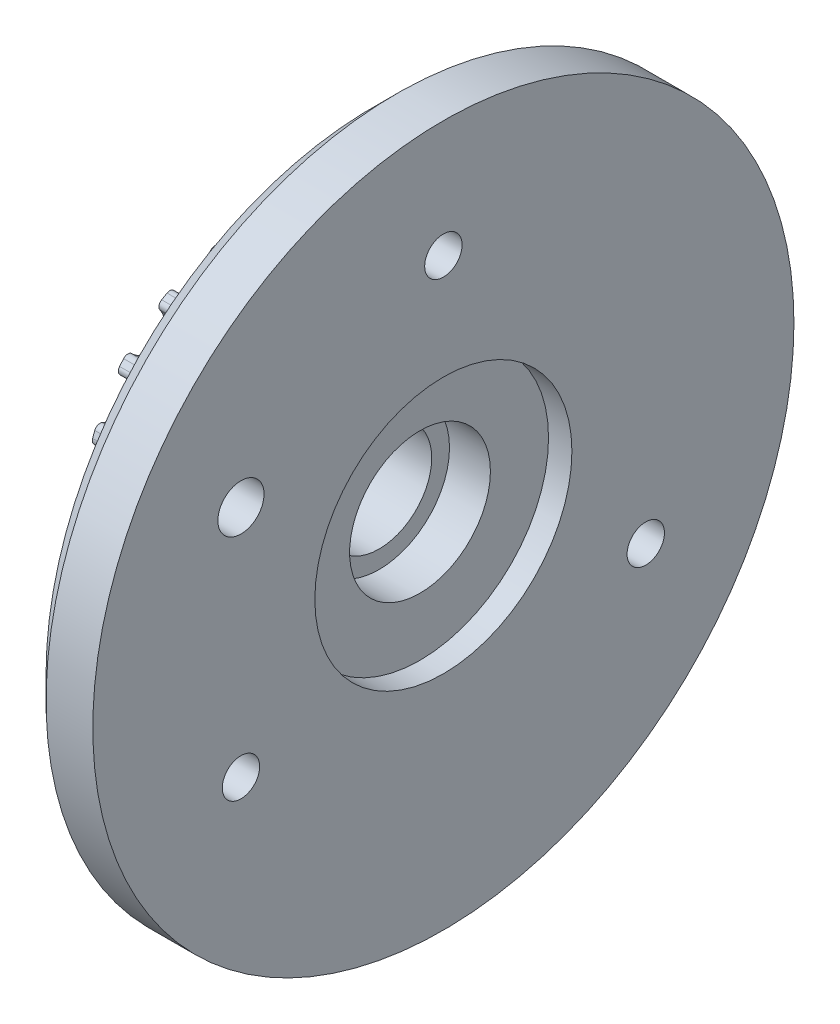
SolidWorks part; units mm, degrees
ref_plane "前视基准面" through (0, 0, 0) normal (0, 0, 1) x (1, 0, 0)
ref_plane "上视基准面" through (0, 0, 0) normal (0, 1, 0) x (1, 0, 0)
ref_plane "右视基准面" through (0, 0, 0) normal (1, 0, 0) x (0, 0, -1)
sketch "草图1" plane through (0, 0, 0) normal (0, 0, 1) x (1, 0, 0)
  line L0 (0, 0) -> (64.8368, 0) construction
  line L1 (0, 2.7888) -> (0, 13.753)
  line L2 (0, 13.753) -> (11, 13.753)
  line L3 (11, 13.753) -> (11, 2.7888)
  line L6 (11, 2.7888) -> (0, 2.7888)
  dimension "B" = 11
  dimension "d" = 5.5776
  dimension "da" = 27.506
revolve "旋转1" add sketch "草图1" angle 360 about L0
sketch "草图6" plane through (0, 0, 0) normal (1, 0, 0) x (0, 0, -1)
  line L0 (0, 0) -> (0, 30.6512) construction
  line L1 (1.5741, 13.1722) -> (1.5484, 12.9629)
  line L2 (2.5975, 13.5055) -> (2.7942, 15.107)
  line L3 (-2.5975, 13.5055) -> (-2.7942, 15.107)
  line L4 (-1.5741, 13.1722) -> (-1.5484, 12.9629)
  circle A0 centre (0, 0) radius 13.753 construction
  circle A1 centre (0, 0) radius 11.593 construction
  arc A2 (-1.5484, 12.9629) -> (1.5484, 12.9629) centre (0, 13.153) ccw
  arc A3 (2.7942, 15.107) -> (-2.7942, 15.107) centre (0, 0) ccw
  arc A4 (1.5741, 13.1722) -> (2.1246, 13.5879) centre (2.0505, 13.1137) cw
  arc A5 (2.1246, 13.5879) -> (2.5975, 13.5055) centre (0, 0) cw
  arc A6 (-2.1246, 13.5879) -> (-2.5975, 13.5055) centre (0, 0) ccw
  arc A7 (-1.5741, 13.1722) -> (-2.1246, 13.5879) centre (-2.0505, 13.1137) ccw
  point P7 (0, 3.25)
  point P8 (0, 28.4912)
  point P15 (1.6334, 13.6557)
  dimension "D1" = 23.186
  dimension "ra" = 0.48
  dimension "rf" = 1.56
  dimension "hg" = 2.16
  dimension "D3" = 0.48
  dimension "D4" = 1.6136
  dimension "angle" = 14
  dimension "bw" = 3.25
extrude "切除-拉伸2" cut sketch "草图6" along normal up to next
ref_axis "基准轴1" through (-1.4, 0, 0) along (1, 0, 0)
pattern_circular "阵列(圆周)3" count 18 over 360 about axis through (-1.4, 0, 0) along (1, 0, 0) of "切除-拉伸2"
sketch "草图7" plane through (11, 0, 0) normal (1, 0, 0) x (0, 0, -1)
  circle A0 centre (0, 0) radius 30
  dimension "D1" = 60
extrude "凸台-拉伸1" add sketch "草图7" along normal blind 6
sketch "草图8" plane through (0, 0, 0) normal (-1, 0, 0) x (0, 0, 1)
  circle A1 centre (0, 0) radius 2.7888 construction
  circle A2 centre (0, 0) radius 2.7888
extrude "凸台-拉伸2" add sketch "草图8" against normal up to surface (11 mm away) up to face at (11, 0, 0)
sketch "草图10" plane through (17, 0, 0) normal (1, 0, 0) x (0, 0, -1)
  circle A0 centre (0, 0) radius 11
  dimension "D1" = 22
extrude "切除-拉伸3" cut sketch "草图10" against normal blind 2
sketch "草图11" plane through (11, 0, 0) normal (-1, 0, 0) x (0, 0, 1)
  circle A0 centre (0, 0) radius 20 construction
  circle A1 centre (0, 20) radius 1.6
  dimension "D1" = 40
  dimension "D2" = 3.2
extrude "切除-拉伸4" cut sketch "草图11" against normal through all
pattern_circular "阵列(圆周)4" count 3 over 360 about axis through (11, 0, 0) along (1, 0, 0) of "切除-拉伸4"
sketch "草图13" plane through (11, 0, 0) normal (-1, 0, 0) x (0, 0, 1)
  circle A0 centre (0, 0) radius 20 construction
  circle A1 centre (17.3205, 10) radius 1.975
  circle A2 centre (0, 20) radius 1.6 construction
  dimension "D1" = 60
  dimension "D2" = 3.95
extrude "切除-拉伸5" cut sketch "草图13" against normal through all
chamfer "倒角1" distance 0.8 angle 45 1 edges at (11, 10, 19.2955)
chamfer "倒角2" distance 2.5 angle 45 3 edges at (11, -11.3856, 16.5205) (11, -8.6144, -18.1205) (11, 20, 1.6)
sketch "草图14" plane through (0, 0, 0) normal (-1, 0, 0) x (0, 0, 1)
  circle A0 centre (0, 0) radius 4
  dimension "D1" = 8
extrude "切除-拉伸6" cut sketch "草图14" along normal blind 10 from surface starting at face at (15, 0, -11)
sketch "草图15" plane through (0, 0, 0) normal (-1, 0, 0) x (0, 0, 1)
  circle A0 centre (0, 0) radius 4.5
  dimension "D1" = 9
extrude "切除-拉伸7" cut sketch "草图15" against normal through all
chamfer "倒角3" distance 2 angle 45 1 edges at (11, 0, -30)
sketch "草图17" plane through (15, 0, 0) normal (1, 0, 0) x (0, 0, -1)
  circle A0 centre (0, 0) radius 6.025
  dimension "D1" = 12.05
extrude "切除-拉伸8" cut sketch "草图17" against normal blind 3.5
sketch "草图18" plane through (0, 0, 0) normal (-1, 0, 0) x (0, 0, 1)
  circle A1 centre (0, 0) radius 6.025
  circle A2 centre (0, 0) radius 6.025
  dimension "D1" = 0
extrude "切除-拉伸9" cut sketch "草图18" against normal blind 3.4
equation "\"D1@草图6\" = \"da@草图1\"  - \"hg@草图6\" - \"hg@草图6\""
equation "\"D3@草图6\" = \"ra@草图6\""
